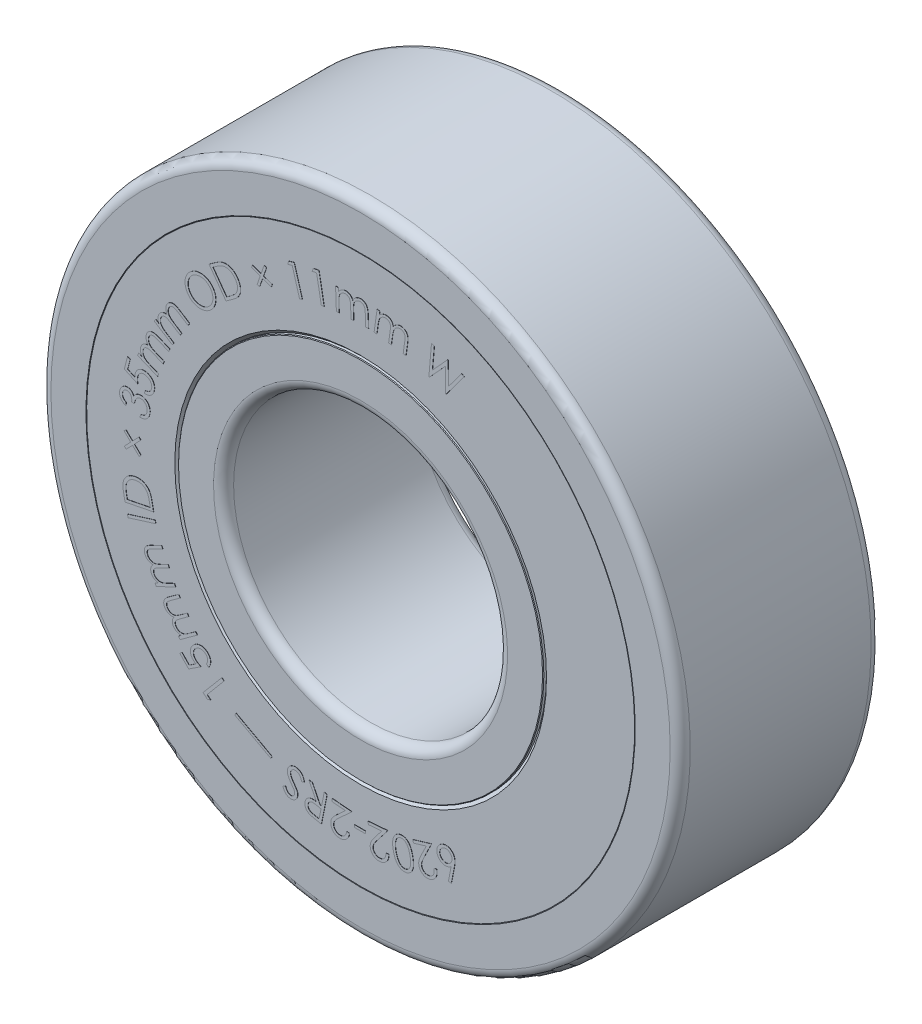
SolidWorks part; units mm, degrees
material "AISI 316 Annealed Stainless Steel Bar (SS)"
ref_plane "Front" through (0, 0, 0) normal (0, 0, 1) x (1, 0, 0)
ref_plane "Top" through (0, 0, 0) normal (0, 1, 0) x (1, 0, 0)
ref_plane "Right" through (0, 0, 0) normal (1, 0, 0) x (0, 0, -1)
sketch "LAYOUT R" plane through (0, 0, 0) normal (1, 0, 0) x (0, 0, -1)
  line L0 (-5.5, 7.5) -> (5.5, 7.5)
  line L1 (5.5, -17.5) -> (-5.5, -17.5) construction
  line L2 (5.5, -17.5) -> (5.5, 17.5) construction
  line L3 (5.5, 17.5) -> (-5.5, 17.5)
  line L4 (-5.5, -17.5) -> (-5.5, 17.5) construction
  line L5 (5.5, -17.5) -> (-5.5, 17.5) construction
  line L6 (5.5, 17.5) -> (-5.5, -17.5) construction
  line L7 (-5.5, 10) -> (5.5, 10)
  line L8 (-5.5, 15) -> (5.5, 15)
  line L11 (-3.81, 0) -> (3.81, 0) construction
  line L12 (-5.5, 17.5) -> (-5.5, 15)
  line L13 (5.5, 17.5) -> (5.5, 15)
  line L14 (-5.5, 15) -> (-5.5, 10)
  line L15 (5.5, 15) -> (5.5, 10)
  line L16 (-5.5, 10) -> (-5.5, 7.5)
  line L17 (5.5, 10) -> (5.5, 7.5)
  line L18 (-5.4945, 15) -> (-5.4945, 10)
  line L19 (5.4945, 15) -> (5.4945, 10)
  point P0 (0, 0)
  point P15 (0, 0)
  dimension "D1" = 11
  dimension "D2" = 35
  dimension "D3" = 7.5
  dimension "D6" = 0.0055
  dimension "D7" = 0.0055
  dimension "D4" = 10
  dimension "D5" = 15
sketch "Sketch R, INNER BODY" plane through (0, 0, 0) normal (1, 0, 0) x (0, 0, -1)
  line L0 (-5.5, 7.5) -> (5.5, 7.5) construction
  line L2 (-5.5, 10) -> (5.5, 10) construction
  line L4 (-5.5, 7.5) -> (5.5, 7.5)
  line L6 (-5.5, 10) -> (5.5, 10)
  line L8 (5.5, 10) -> (5.5, 7.5) construction
  line L9 (-5.5, 10) -> (-5.5, 7.5) construction
  line L10 (5.5, 10) -> (5.5, 7.5)
  line L11 (-5.5, 10) -> (-5.5, 7.5)
  line L12 (-3.81, 0) -> (3.81, 0) construction
  line L13 (-3.81, 0) -> (3.81, 0) construction
sketch "Sketch R, OUTER BODY" plane through (0, 0, 0) normal (1, 0, 0) x (0, 0, -1)
  line L0 (-5.5, 15) -> (5.5, 15) construction
  line L1 (5.5, 17.5) -> (5.5, 15) construction
  line L8 (-3.81, 0) -> (3.81, 0) construction
  line L9 (-3.81, 0) -> (3.81, 0) construction
  line L16 (5.5, 17.5) -> (-5.5, 17.5) construction
  line L17 (-5.5, 17.5) -> (-5.5, 15) construction
  line L18 (-5.5, 15) -> (5.5, 15)
  line L19 (5.5, 17.5) -> (5.5, 15)
  line L22 (5.5, 17.5) -> (-5.5, 17.5)
  line L23 (-5.5, 17.5) -> (-5.5, 15)
sketch "Sketch R, SEAL FACES" plane through (0, 0, 0) normal (1, 0, 0) x (0, 0, -1)
  line L0 (-3.81, 0) -> (3.81, 0) construction
  line L1 (-3.81, 0) -> (3.81, 0) construction
  line L3 (-5.5, 10) -> (5.5, 10) construction
  line L5 (-5.5, 15) -> (5.5, 15) construction
  line L7 (-5.4945, 10) -> (5.4945, 10)
  line L9 (-5.4945, 15) -> (5.4945, 15)
  line L10 (5.4945, 15) -> (5.4945, 10) construction
  line L11 (-5.4945, 15) -> (-5.4945, 10) construction
  line L12 (5.4945, 15) -> (5.4945, 10)
  line L13 (-5.4945, 15) -> (-5.4945, 10)
revolve "Revolve INNER BODY" add sketch "Sketch R, INNER BODY" angle 360 about L13
fillet "Fillet INNER BODY" radius 0.55 2 edges at (0, -7.5, 5.5) (0, -7.5, -5.5)
chamfer "Chamfer INNER BODY" distance 0.035 angle 45 2 edges at (0, -10, -5.5) (0, -10, 5.5)
revolve "Revolve OUTER BODY" add sketch "Sketch R, OUTER BODY" angle 360 about L9
fillet "Fillet OUTER BODY" radius 0.55 2 edges at (0, -17.5, 5.5) (0, -17.5, -5.5)
chamfer "Chamfer OUTER BODY" distance 0.035 angle 45 2 edges at (0, -15, 5.5) (0, -15, -5.5)
revolve "Revolve SEALS" add sketch "Sketch R, SEAL FACES" angle 360 about L1
chamfer "Chamfer SEALS" distance 0.175 angle 45 2 edges at (0, -10, -5.4945) (0, -10, 5.4945)
sketch "Sketch SEAL LABEL 1" plane through (0, 0, 5.4945) normal (0, 0, 1) x (1, 0, 0)
  circle A0 centre (0, 0) radius 11.7 construction
  text T0 "6202-2RS — 15mm ID × 35mm OD × 11mm W" font "Century Gothic" height 1.6
  dimension "D1" = 23.4
extrude "Boss-Extrude SEAL LABEL 1" add sketch "Sketch SEAL LABEL 1" along normal blind 0.013
sketch "Sketch SEAL LABEL 2" plane through (0, 0, -5.4945) normal (0, 0, -1) x (-1, 0, 0)
  circle A0 centre (0, 0) radius 11.7 construction
  text T0 "6202-2RS — 15mm ID × 35mm OD × 11mm W" font "Century Gothic" height 1.6
  dimension "D1" = 23.4
extrude "Boss-Extrude SEAL LABEL 2" add sketch "Sketch SEAL LABEL 2" along normal blind 0.013
equation "\"_i__BORE\"= 15"
equation "\"_i__OUTSIDE_DIAMETER\"= 35"
equation "\"_i__WIDTH\"= 11"
equation "\"_user_applied_FONT_SIZE\"= int ( \"BODY_SPAN__SEAL__OF_RADIUS\" * \"g_param__FONT_SIZE_RATIO\" * 100 ) / 100'MANUALLY ASSIGN TO FONT"
equation "\"BODY__HALF_WIDTH\"= \"_i__WIDTH\" / 2"
equation "\"BODY_SPAN___OF_DIAMETER\"= \"_i__OUTSIDE_DIAMETER\" - \"_i__BORE\""
equation "\"BODY_SPAN___OF_RADIUS\"= \"BODY_SPAN___OF_DIAMETER\" / 2"
equation "\"BODY_SPAN__BORE_AND_OD__OF RADIUS\"= ( \"BODY_SPAN___OF_RADIUS\" - \"BODY_SPAN__SEAL__OF_RADIUS\" ) / 2"
equation "\"BODY_SPAN__SEAL__OF_RADIUS\"= \"BODY_SPAN___OF_RADIUS\" * \"g_param__SEAL_PANEL_SPAN__RATIO_OF_BODY_RADIAN\""
equation "\"BORE__RADIUS\"= \"_i__BORE\" / 2"
equation "\"CORNER_RADII\"= \"_i__WIDTH\" * \"g_param__CORNER_RADII__RATIO_TO_WIDTH\""
equation "\"RING_INNER__OUTSIDE_RADIUS\"= \"BORE__RADIUS\" + \"BODY_SPAN__BORE_AND_OD__OF RADIUS\""
equation "\"RING_OUTER__OUTSIDE_RADIUS\"= ( \"_i__OUTSIDE_DIAMETER\" / 2 ) - \"BODY_SPAN__BORE_AND_OD__OF RADIUS\""
equation "\"SEAL_CHAMFERS\"= \"_i__OUTSIDE_DIAMETER\" * \"g_param__SEAL_CHAMFERS__RATIO_TO_OD\""
equation "\"SEAL_FACE_INSET\"= \"SIDE_FACE_CHAMFERS\""
equation "\"SIDE_FACE_CHAMFERS\"= \"_i__OUTSIDE_DIAMETER\" * \"g_param__SIDE_CHAMFERS__RATIO_TO_OD\""
equation "\"TEXT_RADIUS\"= \"_i__BORE\" + ( \"BODY_SPAN___OF_DIAMETER\" / 2 ) - \"_user_applied_FONT_SIZE\""
equation "\"D1@Boss-Extrude SEAL LABEL 1\" = \"g_param__INDICIA__EXTRUSION_HEIGHT\""
equation "\"D1@Boss-Extrude SEAL LABEL 2\" = \"g_param__INDICIA__EXTRUSION_HEIGHT\""
equation "\"D1@Chamfer INNER BODY\"=\"SIDE_FACE_CHAMFERS\""
equation "\"D1@Chamfer OUTER BODY\"=\"SIDE_FACE_CHAMFERS\""
equation "\"D1@Chamfer SEALS\"=\"SEAL_CHAMFERS\""
equation "\"D1@Fillet INNER BODY\"=\"CORNER_RADII\""
equation "\"D1@Fillet OUTER BODY\"=\"CORNER_RADII\""
equation "\"D1@LAYOUT R\"=\"_i__WIDTH\""
equation "\"D1@Sketch SEAL LABEL 1\" = \"TEXT_RADIUS\""
equation "\"D1@Sketch SEAL LABEL 2\" = \"TEXT_RADIUS\""
equation "\"D2@LAYOUT R\"=\"_i__OUTSIDE_DIAMETER\""
equation "\"D3@LAYOUT R\"=\"BORE__RADIUS\""
equation "\"D4@LAYOUT R\"=\"RING_INNER__OUTSIDE_RADIUS\""
equation "\"D5@LAYOUT R\"=\"RING_OUTER__OUTSIDE_RADIUS\""
equation "\"g_param__CORNER_RADII__RATIO_TO_WIDTH\"= 0.05'ISO MAX IS 0.07 WHERE WIDTH IS LESS THAN DIAMETER"
equation "\"g_param__FONT_SIZE_RATIO\"= 0.32'EXPRESSES RADIAL PROPORTION OF SEAL FACE"
equation "\"g_param__INDICIA__EXTRUSION_HEIGHT\"=0.013'RAISED INDICIA ON SEAL FACES"
equation "\"g_param__SEAL_CHAMFERS__RATIO_TO_OD\"= 0.005"
equation "\"g_param__SEAL_PANEL_SPAN__RATIO_OF_BODY_RADIAN\"= 0.5'ISO-UNSPECIFIED"
equation "\"g_param__SIDE_CHAMFERS__RATIO_TO_OD\"= 0.001'NOT ISO-SPECIFIED"
